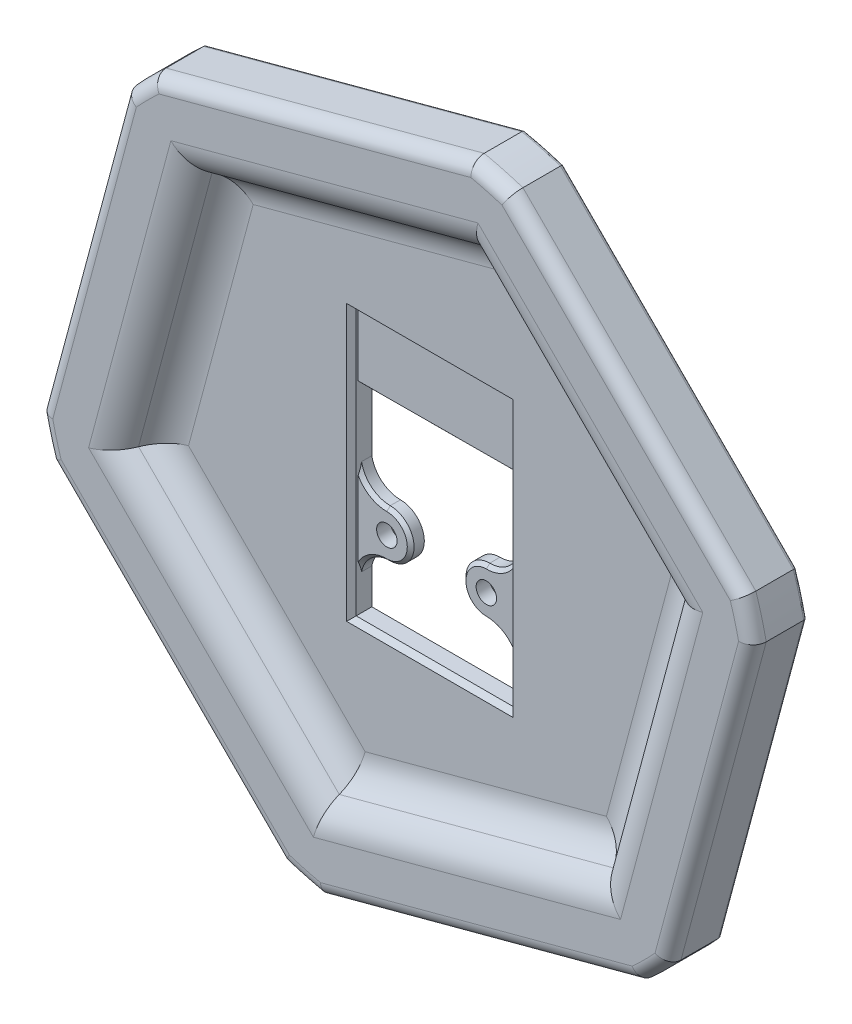
SolidWorks part; units mm, degrees
ref_plane "Спереди" through (0, 0, 0) normal (0, 0, 1) x (1, 0, 0)
ref_plane "Сверху" through (0, 0, 0) normal (0, 1, 0) x (1, 0, 0)
ref_plane "Справа" through (0, 0, 0) normal (1, 0, 0) x (0, 0, -1)
sketch "Эскиз1" plane through (0, 0, 0) normal (0, 0, 1) x (1, 0, 0)
  circle A1 centre (0, 0) radius 53.5
  circle A5 centre (0, 0) radius 39
extrude "Бобышка-Вытянуть1" add sketch "Эскиз1" along normal blind 65
sketch "Эскиз2" plane through (0, 0, 65) normal (0, 0, 1) x (1, 0, 0)
  line L0 (0, 0) -> (-8, 8) construction
  line L1 (-8, 8) -> (-59.1146, 59.1146) construction
  line L2 (-34.0759, 34.0759) -> (-46.5485, -12.4726)
  line L3 (-35.7089, 35.7089) -> (-48.7793, -13.0704)
  line L4 (-48.7793, -13.0704) -> (-13.0704, -48.7793)
  line L5 (-13.0704, -48.7793) -> (35.7089, -35.7089)
  line L6 (35.7089, -35.7089) -> (48.7793, 13.0704)
  line L7 (48.7793, 13.0704) -> (13.0704, 48.7793)
  line L8 (13.0704, 48.7793) -> (-35.7089, 35.7089)
  line L9 (-46.5485, -12.4726) -> (-12.4726, -46.5485)
  line L10 (-12.4726, -46.5485) -> (34.0759, -34.0759)
  line L11 (34.0759, -34.0759) -> (46.5485, 12.4726)
  line L12 (46.5485, 12.4726) -> (12.4726, 46.5485)
  line L13 (12.4726, 46.5485) -> (-34.0759, 34.0759)
  circle A0 centre (0, 0) radius 43.7343 construction
  dimension "D1" = 101
  dimension "D2" = 2
extrude "Вырез-Вытянуть1" cut sketch "Эскиз2" against normal blind 3
sketch "Эскиз3" plane through (0, 0, 65) normal (0, 0, 1) x (1, 0, 0)
  line L0 (43.7602, 11.7255) -> (11.7255, 43.7602)
  line L1 (11.7255, 43.7602) -> (-32.0347, 32.0347)
  line L2 (-32.0347, 32.0347) -> (-43.7602, -11.7255)
  line L3 (-43.7602, -11.7255) -> (-11.7255, -43.7602)
  line L4 (-11.7255, -43.7602) -> (32.0347, -32.0347)
  line L5 (32.0347, -32.0347) -> (43.7602, 11.7255)
  line L6 (46.5485, 12.4726) -> (12.4726, 46.5485)
  line L7 (12.4726, 46.5485) -> (-34.0759, 34.0759)
  line L8 (-34.0759, 34.0759) -> (-46.5485, -12.4726)
  line L9 (-46.5485, -12.4726) -> (-12.4726, -46.5485)
  line L10 (-12.4726, -46.5485) -> (34.0759, -34.0759)
  line L11 (34.0759, -34.0759) -> (46.5485, 12.4726)
  line L12 (46.5485, 12.4726) -> (12.4726, 46.5485)
  line L13 (12.4726, 46.5485) -> (-34.0759, 34.0759)
  line L14 (-34.0759, 34.0759) -> (-46.5485, -12.4726)
  line L15 (-46.5485, -12.4726) -> (-12.4726, -46.5485)
  line L16 (-12.4726, -46.5485) -> (34.0759, -34.0759)
  line L17 (34.0759, -34.0759) -> (46.5485, 12.4726)
  dimension "D1" = 0
  dimension "D2" = 2.5
extrude "Бобышка-Вытянуть2" add sketch "Эскиз3" along normal blind 3
fillet "Скругление2" radius 3 1 edges at (39, 0, 65)
sketch "Эскиз4" plane through (0, 0, 65) normal (0, 0, 1) x (1, 0, 0)
  line L12 (14.2658, 53.2407) -> (-38.9749, 38.9749)
  line L13 (53.2407, 14.2658) -> (14.2658, 53.2407)
  line L14 (38.9749, -38.9749) -> (53.2407, 14.2658)
  line L15 (-14.2658, -53.2407) -> (38.9749, -38.9749)
  line L16 (-53.2407, -14.2658) -> (-14.2658, -53.2407)
  line L17 (-38.9749, 38.9749) -> (-53.2407, -14.2658)
  line L18 (14.2658, 53.2407) -> (-38.9749, 38.9749)
  line L19 (53.2407, 14.2658) -> (14.2658, 53.2407)
  line L20 (38.9749, -38.9749) -> (53.2407, 14.2658)
  line L21 (-14.2658, -53.2407) -> (38.9749, -38.9749)
  line L22 (-53.2407, -14.2658) -> (-14.2658, -53.2407)
  line L23 (-38.9749, 38.9749) -> (-53.2407, -14.2658)
  circle A2 centre (0, 0) radius 58.5
  circle A3 centre (0, 0) radius 58.5
  dimension "D1" = 4
  dimension "D2" = 5
extrude "Вырез-Вытянуть2" cut sketch "Эскиз4" against normal blind 105 contours L18 L23 L22 L21 L20 L19 | A3
fillet "Скругление3" radius 2 12 edges at (13.8468, 51.677, 65) (-12.3545, 46.1078, 65) (-37.8302, 37.8302, 65) (-46.1078, 12.3545, 65) (-51.677, -13.8468, 65) (-33.7532, -33.7532, 65) (-13.8468, -51.677, 65) (37.8302, -37.8302, 65) (12.3545, -46.1078, 65) (33.7532, 33.7532, 65) (51.677, 13.8468, 65) (46.1078, -12.3545, 65)
sketch "Эскиз5" plane through (0, 0, 65) normal (0, 0, 1) x (1, 0, 0)
  line L2 (-11.7255, -43.7602) -> (-4.3237, -41.7769)
  line L3 (-17.144, -38.3417) -> (-11.7255, -43.7602)
  line L4 (-11.7255, -43.7602) -> (-4.3237, -41.7769)
  line L5 (-17.144, -38.3417) -> (-11.7255, -43.7602)
  line L8 (-43.7602, -11.7255) -> (-38.3417, -17.144)
  line L9 (-41.7769, -4.3237) -> (-43.7602, -11.7255)
  line L12 (-32.0347, 32.0347) -> (-34.018, 24.6329)
  line L13 (-24.6329, 34.018) -> (-32.0347, 32.0347)
  line L16 (11.7255, 43.7602) -> (4.3237, 41.7769)
  line L17 (17.144, 38.3417) -> (11.7255, 43.7602)
  line L20 (43.7602, 11.7255) -> (38.3417, 17.144)
  line L21 (41.7769, 4.3237) -> (43.7602, 11.7255)
  line L24 (32.0347, -32.0347) -> (34.018, -24.6329)
  line L25 (24.6329, -34.018) -> (32.0347, -32.0347)
  arc A1 (-17.144, -38.3417) -> (-4.3237, -41.7769) centre (0, 0) ccw
  arc A3 (-17.144, -38.3417) -> (-4.3237, -41.7769) centre (0, 0) ccw
  arc A4 (-41.7769, -4.3237) -> (-38.3417, -17.144) centre (0, 0) ccw
  arc A6 (-24.6329, 34.018) -> (-34.018, 24.6329) centre (0, 0) ccw
  arc A8 (17.144, 38.3417) -> (4.3237, 41.7769) centre (0, 0) ccw
  arc A10 (41.7769, 4.3237) -> (38.3417, 17.144) centre (0, 0) ccw
  arc A12 (24.6329, -34.018) -> (34.018, -24.6329) centre (0, 0) ccw
  dimension "D1" = 0
extrude "Бобышка-Вытянуть3" add sketch "Эскиз5" along normal blind 3
sketch "Эскиз6" plane through (0, 0, 0) normal (0, 0, -1) x (-1, 0, 0)
  circle A0 centre (-11.841, 44.1911) radius 1.25 construction
  circle A1 centre (32.3501, 32.3501) radius 1.25 construction
  circle A2 centre (44.1911, -11.841) radius 1.25 construction
  circle A3 centre (11.841, -44.1911) radius 1.25 construction
  circle A4 centre (-32.3501, -32.3501) radius 1.25 construction
  circle A5 centre (-44.1911, 11.841) radius 1.25 construction
  circle A6 centre (-11.841, 44.1911) radius 1.25
  circle A7 centre (32.3501, 32.3501) radius 1.25
  circle A8 centre (44.1911, -11.841) radius 1.25
  circle A9 centre (11.841, -44.1911) radius 1.25
  circle A10 centre (-32.3501, -32.3501) radius 1.25
  circle A11 centre (-44.1911, 11.841) radius 1.25
extrude "Вырез-Вытянуть3" cut sketch "Эскиз6" against normal blind 15
sketch "Эскиз7" plane through (-12.3545, 46.1078, 0) normal (-0.2588, 0.9659, 0) x (0.9659, 0.2588, 0)
  line L3 (0, 0) -> (0, -5) construction
  line L4 (0, -5) -> (0, -78.0432) construction
  circle A0 centre (0, -17) radius 8
  point P2 (0, -5)
  point P6 (0, -17)
  dimension "D2" = 16
  dimension "D1" = 12
extrude "Вырез-Вытянуть4" cut sketch "Эскиз7" against normal blind 10 contours A0
sketch "Эскиз9" plane through (-12.3545, 46.1078, 0) normal (-0.2588, 0.9659, 0) x (0.9659, 0.2588, 0)
  circle A2 centre (0, -17) radius 6
  dimension "D1" = 12
extrude "Вытянуть-Тонкостенный1" add sketch "Эскиз9" against normal blind 6 thin thin type one direction wall 3
sketch "Эскиз10" plane through (-12.3545, 46.1078, 0) normal (-0.2588, 0.9659, 0) x (0.9659, 0.2588, 0)
  circle A2 centre (0, -17) radius 8.5
  dimension "D1" = 17
extrude "Вырез-Вытянуть5" cut sketch "Эскиз10" against normal blind 2
sketch "Эскиз11" plane through (0, 0, 0) normal (0, 0, -1) x (-1, 0, 0)
  line L7 (-16.6698, 50.8367) -> (-50.8367, 16.6698)
  line L8 (-52.3608, 10.9819) -> (-39.8548, -35.691)
  line L9 (-35.691, -39.8548) -> (10.9819, -52.3608)
  line L10 (16.6698, -50.8367) -> (50.8367, -16.6698)
  line L11 (52.3608, -10.9819) -> (39.8548, 35.691)
  line L12 (35.691, 39.8548) -> (-10.9819, 52.3608)
  line L13 (-16.6698, 50.8367) -> (-50.8367, 16.6698)
  line L14 (-52.3608, 10.9819) -> (-39.8548, -35.691)
  line L15 (-35.691, -39.8548) -> (10.9819, -52.3608)
  line L16 (16.6698, -50.8367) -> (50.8367, -16.6698)
  line L17 (52.3608, -10.9819) -> (39.8548, 35.691)
  line L18 (35.691, 39.8548) -> (-10.9819, 52.3608)
  arc A7 (-50.8367, 16.6698) -> (-52.3608, 10.9819) centre (0, 0) ccw
  arc A8 (-39.8548, -35.691) -> (-35.691, -39.8548) centre (0, 0) ccw
  arc A9 (10.9819, -52.3608) -> (16.6698, -50.8367) centre (0, 0) ccw
  arc A10 (50.8367, -16.6698) -> (52.3608, -10.9819) centre (0, 0) ccw
  arc A11 (39.8548, 35.691) -> (35.691, 39.8548) centre (0, 0) ccw
  arc A12 (-10.9819, 52.3608) -> (-16.6698, 50.8367) centre (0, 0) ccw
  arc A13 (-50.8367, 16.6698) -> (-52.3608, 10.9819) centre (0, 0) ccw
  arc A14 (-39.8548, -35.691) -> (-35.691, -39.8548) centre (0, 0) ccw
  arc A15 (10.9819, -52.3608) -> (16.6698, -50.8367) centre (0, 0) ccw
  arc A16 (50.8367, -16.6698) -> (52.3608, -10.9819) centre (0, 0) ccw
  arc A17 (39.8548, 35.691) -> (35.691, 39.8548) centre (0, 0) ccw
  arc A18 (-10.9819, 52.3608) -> (-16.6698, 50.8367) centre (0, 0) ccw
  dimension "D1" = 0
extrude "Вырез-Вытянуть6" cut sketch "Эскиз11" against normal blind 50
sketch "Эскиз13" plane through (0, 0, 50) normal (0, 0, -1) x (-1, 0, 0)
  line L0 (35.7089, 35.7089) -> (48.7793, -13.0704) construction
  line L1 (48.7793, -13.0704) -> (13.0704, -48.7793) construction
  line L2 (13.0704, -48.7793) -> (-35.7089, -35.7089) construction
  line L3 (-35.7089, -35.7089) -> (-48.7793, 13.0704) construction
  line L4 (-13.0704, 48.7793) -> (35.7089, 35.7089) construction
  line L5 (-48.7793, 13.0704) -> (-13.0704, 48.7793) construction
  line L6 (35.7089, 35.7089) -> (48.7793, -13.0704)
  line L7 (48.7793, -13.0704) -> (13.0704, -48.7793)
  line L8 (13.0704, -48.7793) -> (-35.7089, -35.7089)
  line L9 (-35.7089, -35.7089) -> (-48.7793, 13.0704)
  line L10 (-13.0704, 48.7793) -> (35.7089, 35.7089)
  line L11 (-48.7793, 13.0704) -> (-13.0704, 48.7793)
  line L24 (45.4332, -12.1738) -> (33.2594, 33.2594)
  line L25 (12.1738, -45.4332) -> (45.4332, -12.1738)
  line L26 (-33.2594, -33.2594) -> (12.1738, -45.4332)
  line L27 (-45.4332, 12.1738) -> (-33.2594, -33.2594)
  line L28 (-12.1738, 45.4332) -> (-45.4332, 12.1738)
  line L29 (33.2594, 33.2594) -> (-12.1738, 45.4332)
  line L30 (45.4332, -12.1738) -> (33.2594, 33.2594)
  line L31 (12.1738, -45.4332) -> (45.4332, -12.1738)
  line L32 (-33.2594, -33.2594) -> (12.1738, -45.4332)
  line L33 (-45.4332, 12.1738) -> (-33.2594, -33.2594)
  line L34 (-12.1738, 45.4332) -> (-45.4332, 12.1738)
  line L35 (33.2594, 33.2594) -> (-12.1738, 45.4332)
  dimension "D1" = 1
extrude "Вырез-Вытянуть7" cut sketch "Эскиз13" against normal blind 6
fillet "Скругление4" radius 1 1 edges at (-39, 0, 50)
fillet "Скругление5" radius 0.5 6 edges at (-42.2441, 11.3193, 56) (-30.9248, -30.9248, 50) (11.3193, -42.2441, 50) (42.2441, -11.3193, 50) (30.9248, 30.9248, 50) (-11.3193, 42.2441, 50)
fillet "Скругление6" radius 0.5 6 edges at (39.3463, -10.5428, 50) (10.5428, -39.3463, 56) (-28.8035, -28.8035, 50) (-39.3463, 10.5428, 56) (-10.5428, 39.3463, 56) (28.8035, 28.8035, 50)
sketch "Эскиз14" plane through (0, 0, 65) normal (0, 0, 1) x (1, 0, 0)
  line L0 (-38.0477, 34.7076) -> (-50.3041, -11.0338) construction
  line L1 (11.0338, 50.3041) -> (-34.7076, 38.0477) construction
  line L2 (49.0816, 15.5965) -> (15.5965, 49.0816) construction
  line L3 (38.0477, -34.7076) -> (50.3041, 11.0338) construction
  line L4 (-49.0816, -15.5965) -> (-15.5965, -49.0816) construction
  line L5 (-11.0338, -50.3041) -> (34.7076, -38.0477) construction
  line L6 (-38.0477, 34.7076) -> (-50.3041, -11.0338)
  line L7 (11.0338, 50.3041) -> (-34.7076, 38.0477)
  line L8 (49.0816, 15.5965) -> (15.5965, 49.0816)
  line L9 (38.0477, -34.7076) -> (50.3041, 11.0338)
  line L10 (-49.0816, -15.5965) -> (-15.5965, -49.0816)
  line L11 (-11.0338, -50.3041) -> (34.7076, -38.0477)
  arc A0 (-50.3041, -11.0338) -> (-49.0816, -15.5965) centre (0, 0) ccw construction
  arc A1 (-34.7076, 38.0477) -> (-38.0477, 34.7076) centre (0, 0) ccw construction
  arc A2 (15.5965, 49.0816) -> (11.0338, 50.3041) centre (0, 0) ccw construction
  arc A3 (50.3041, 11.0338) -> (49.0816, 15.5965) centre (0, 0) ccw construction
  arc A4 (34.7076, -38.0477) -> (38.0477, -34.7076) centre (0, 0) ccw construction
  arc A5 (-15.5965, -49.0816) -> (-11.0338, -50.3041) centre (0, 0) ccw construction
  arc A6 (-50.3041, -11.0338) -> (-49.0816, -15.5965) centre (0, 0) ccw
  arc A7 (-34.7076, 38.0477) -> (-38.0477, 34.7076) centre (0, 0) ccw
  arc A8 (15.5965, 49.0816) -> (11.0338, 50.3041) centre (0, 0) ccw
  arc A9 (50.3041, 11.0338) -> (49.0816, 15.5965) centre (0, 0) ccw
  arc A10 (34.7076, -38.0477) -> (38.0477, -34.7076) centre (0, 0) ccw
  arc A11 (-15.5965, -49.0816) -> (-11.0338, -50.3041) centre (0, 0) ccw
extrude "Вырез-Вытянуть8" cut sketch "Эскиз14" along normal blind 5
sketch "Эскиз16" plane through (0, 0, 50) normal (0, 0, -1) x (-1, 0, 0)
  line L6 (-16.6698, 50.8367) -> (-50.8367, 16.6698)
  line L7 (-52.3608, 10.9819) -> (-39.8548, -35.691)
  line L8 (-35.691, -39.8548) -> (10.9819, -52.3608)
  line L9 (16.6698, -50.8367) -> (50.8367, -16.6698)
  line L10 (52.3608, -10.9819) -> (39.8548, 35.691)
  line L11 (35.691, 39.8548) -> (-10.9819, 52.3608)
  line L12 (-16.6698, 50.8367) -> (-50.8367, 16.6698)
  line L13 (-52.3608, 10.9819) -> (-39.8548, -35.691)
  line L14 (-35.691, -39.8548) -> (10.9819, -52.3608)
  line L15 (16.6698, -50.8367) -> (50.8367, -16.6698)
  line L16 (52.3608, -10.9819) -> (39.8548, 35.691)
  line L17 (35.691, 39.8548) -> (-10.9819, 52.3608)
  arc A6 (-10.9819, 52.3608) -> (-16.6698, 50.8367) centre (0, 0) ccw
  arc A7 (-50.8367, 16.6698) -> (-52.3608, 10.9819) centre (0, 0) ccw
  arc A8 (-39.8548, -35.691) -> (-35.691, -39.8548) centre (0, 0) ccw
  arc A9 (10.9819, -52.3608) -> (16.6698, -50.8367) centre (0, 0) ccw
  arc A10 (50.8367, -16.6698) -> (52.3608, -10.9819) centre (0, 0) ccw
  arc A11 (39.8548, 35.691) -> (35.691, 39.8548) centre (0, 0) ccw
  arc A12 (-10.9819, 52.3608) -> (-16.6698, 50.8367) centre (0, 0) ccw
  arc A13 (-50.8367, 16.6698) -> (-52.3608, 10.9819) centre (0, 0) ccw
  arc A14 (-39.8548, -35.691) -> (-35.691, -39.8548) centre (0, 0) ccw
  arc A15 (10.9819, -52.3608) -> (16.6698, -50.8367) centre (0, 0) ccw
  arc A16 (50.8367, -16.6698) -> (52.3608, -10.9819) centre (0, 0) ccw
  arc A17 (39.8548, 35.691) -> (35.691, 39.8548) centre (0, 0) ccw
  dimension "D1" = 0
extrude "Вырез-Вытянуть9" cut sketch "Эскиз16" against normal blind 5
sketch "Эскиз23" plane through (0, 0, 56) normal (0, 0, -1) x (-1, 0, 0)
  line L0 (13.0704, -48.7793) -> (48.371, -13.4786) construction
  line L1 (45.4332, -12.1738) -> (12.1738, -45.4332) construction
  line L2 (12.1738, -45.4332) -> (-33.2594, -33.2594) construction
  line L3 (-33.2594, -33.2594) -> (-45.4332, 12.1738) construction
  line L4 (-35.7089, -35.7089) -> (-48.7793, 13.0704) construction
  line L5 (-35.7089, -35.7089) -> (13.0704, -48.7793) construction
  line L6 (13.0704, -48.7793) -> (48.371, -13.4786)
  line L7 (45.4332, -12.1738) -> (12.1738, -45.4332)
  line L8 (12.1738, -45.4332) -> (-33.2594, -33.2594)
  line L9 (-33.2594, -33.2594) -> (-45.4332, 12.1738)
  line L10 (-35.7089, -35.7089) -> (-48.7793, 13.0704)
  line L11 (-35.7089, -35.7089) -> (13.0704, -48.7793)
  line L12 (-45.4332, 12.1738) -> (-12.1738, 45.4332) construction
  line L13 (-48.7793, 13.0704) -> (-13.0704, 48.7793) construction
  line L14 (-45.4332, 12.1738) -> (-12.1738, 45.4332)
  line L15 (-48.7793, 13.0704) -> (-13.0704, 48.7793)
  line L16 (33.2594, 33.2594) -> (-12.1738, 45.4332) construction
  line L17 (-13.0704, 48.7793) -> (35.7089, 35.7089) construction
  line L18 (33.2594, 33.2594) -> (-12.1738, 45.4332)
  line L19 (-13.0704, 48.7793) -> (35.7089, 35.7089)
  line L20 (33.2594, 33.2594) -> (45.4332, -12.1738) construction
  line L21 (35.7089, 35.7089) -> (48.7793, -13.0704) construction
  line L22 (33.2594, 33.2594) -> (45.4332, -12.1738)
  line L23 (35.7089, 35.7089) -> (48.7793, -13.0704)
  line M7 (45.8414, -11.7655) -> (11.7655, -45.8414)
  line M8 (11.7655, -45.8414) -> (-33.11, -33.8171)
  line M9 (-33.11, -33.8171) -> (-45.4332, 12.1738)
  line M10 (-45.4332, 12.1738) -> (-11.7655, 45.8414)
  line M11 (-11.7655, 45.8414) -> (33.6677, 33.6677)
  line M12 (33.6677, 33.6677) -> (45.8414, -11.7655)
  line M13 (13.0704, -48.7793) -> (48.371, -13.4786)
  line M14 (48.371, -13.4786) -> (35.1512, 35.8583)
  line M15 (35.1512, 35.8583) -> (-13.0704, 48.7793)
  line M16 (-13.0704, 48.7793) -> (-48.7793, 13.0704)
  line M17 (-48.7793, 13.0704) -> (-35.7089, -35.7089)
  line M18 (-35.7089, -35.7089) -> (13.0704, -48.7793)
extrude "Вырез-Вытянуть11" cut sketch "Эскиз23" against normal blind 4 contours M18 M13 M14 M15 M16 M17 M12 M7 M8 M9 M10 M11 region at (10.9629, -40.9142, 56)
sketch "Эскиз25" plane through (0, 0, 55) normal (0, 0, -1) x (-1, 0, 0)
  line L0 (-35.691, -39.8548) -> (10.9819, -52.3608) construction
  line L1 (16.6698, -50.8367) -> (50.8367, -16.6698) construction
  line L2 (52.3608, -10.9819) -> (39.8548, 35.691) construction
  line L3 (35.691, 39.8548) -> (-10.9819, 52.3608) construction
  line L4 (-16.6698, 50.8367) -> (-50.8367, 16.6698) construction
  line L5 (-52.3608, 10.9819) -> (-39.8548, -35.691) construction
  line L6 (-35.691, -39.8548) -> (10.9819, -52.3608)
  line L7 (16.6698, -50.8367) -> (50.8367, -16.6698)
  line L8 (52.3608, -10.9819) -> (39.8548, 35.691)
  line L9 (35.691, 39.8548) -> (-10.9819, 52.3608)
  line L10 (-16.6698, 50.8367) -> (-50.8367, 16.6698)
  line L11 (-52.3608, 10.9819) -> (-39.8548, -35.691)
  arc A0 (-39.8548, -35.691) -> (-35.691, -39.8548) centre (0, 0) ccw construction
  arc A1 (10.9819, -52.3608) -> (16.6698, -50.8367) centre (0, 0) ccw construction
  arc A2 (50.8367, -16.6698) -> (52.3608, -10.9819) centre (0, 0) ccw construction
  arc A3 (39.8548, 35.691) -> (35.691, 39.8548) centre (0, 0) ccw construction
  arc A4 (-10.9819, 52.3608) -> (-16.6698, 50.8367) centre (0, 0) ccw construction
  arc A5 (-50.8367, 16.6698) -> (-52.3608, 10.9819) centre (0, 0) ccw construction
  arc A6 (-39.8548, -35.691) -> (-35.691, -39.8548) centre (0, 0) ccw
  arc A7 (10.9819, -52.3608) -> (16.6698, -50.8367) centre (0, 0) ccw
  arc A8 (50.8367, -16.6698) -> (52.3608, -10.9819) centre (0, 0) ccw
  arc A9 (39.8548, 35.691) -> (35.691, 39.8548) centre (0, 0) ccw
  arc A10 (-10.9819, 52.3608) -> (-16.6698, 50.8367) centre (0, 0) ccw
  arc A11 (-50.8367, 16.6698) -> (-52.3608, 10.9819) centre (0, 0) ccw
extrude "Вырез-Вытянуть12" cut sketch "Эскиз25" against normal blind 2
fillet "Скругление7" radius 0.5 19 edges at (-39, 0, 57) (42.2441, -11.3193, 57) (11.3193, -42.2441, 57) (-30.7207, -31.1289, 57) (-41.7611, 11.1899, 57) (-11.0404, 42.3188, 57) (30.9248, 30.9248, 57) (46.1078, -12.3545, 57) (51.677, 13.8468, 57) (33.7532, 33.7532, 57) (13.8468, 51.677, 57) (-12.3545, 46.1078, 57) (-37.8302, 37.8302, 57) (-46.1078, 12.3545, 57) (-51.677, -13.8468, 57) (-33.7532, -33.7532, 57) (-13.8468, -51.677, 57) (12.3545, -46.1078, 57) (37.8302, -37.8302, 57)
sketch "Эскиз27" plane through (0, 0, 57) normal (0, 0, -1) x (-1, 0, 0)
  line L12 (-31.477, -32.1841) -> (11.1678, -43.6107)
  line L13 (11.1678, -43.6107) -> (43.6107, -11.1678)
  line L14 (43.6107, -11.1678) -> (32.0347, 32.0347)
  line L15 (32.0347, 32.0347) -> (-11.1678, 43.6107)
  line L16 (-11.1678, 43.6107) -> (-43.2025, 11.5761)
  line L17 (-43.2025, 11.5761) -> (-31.477, -32.1841)
  line L18 (-31.477, -32.1841) -> (11.1678, -43.6107)
  line L19 (11.1678, -43.6107) -> (43.6107, -11.1678)
  line L20 (43.6107, -11.1678) -> (32.0347, 32.0347)
  line L21 (32.0347, 32.0347) -> (-11.1678, 43.6107)
  line L22 (-11.1678, 43.6107) -> (-43.2025, 11.5761)
  line L23 (-43.2025, 11.5761) -> (-31.477, -32.1841)
  dimension "D1" = 2
extrude "Вырез-Вытянуть13" cut sketch "Эскиз27" against normal blind 9
sketch "Эскиз28" plane through (0, 0, 65) normal (0, 0, 1) x (1, 0, 0)
  line L12 (-32.4429, 32.4429) -> (-44.3178, -11.8749)
  line L13 (11.8749, 44.3178) -> (-32.4429, 32.4429)
  line L14 (44.3178, 11.8749) -> (11.8749, 44.3178)
  line L15 (32.4429, -32.4429) -> (44.3178, 11.8749)
  line L16 (-11.8749, -44.3178) -> (32.4429, -32.4429)
  line L17 (-44.3178, -11.8749) -> (-11.8749, -44.3178)
  line L18 (-32.4429, 32.4429) -> (-44.3178, -11.8749)
  line L19 (11.8749, 44.3178) -> (-32.4429, 32.4429)
  line L20 (44.3178, 11.8749) -> (11.8749, 44.3178)
  line L21 (32.4429, -32.4429) -> (44.3178, 11.8749)
  line L22 (-11.8749, -44.3178) -> (32.4429, -32.4429)
  line L23 (-44.3178, -11.8749) -> (-11.8749, -44.3178)
  dimension "D1" = 2
extrude "Бобышка-Вытянуть4" add sketch "Эскиз28" against normal blind 8
sketch "Эскиз29" plane through (0, 0, 65) normal (0, 0, 1) x (1, 0, 0)
  line L12 (-29.9934, 29.9934) -> (-40.9718, -10.9784)
  line L13 (-40.9718, -10.9784) -> (-10.9784, -40.9718)
  line L14 (-10.9784, -40.9718) -> (29.9934, -29.9934)
  line L15 (29.9934, -29.9934) -> (40.9718, 10.9784)
  line L16 (40.9718, 10.9784) -> (10.9784, 40.9718)
  line L17 (10.9784, 40.9718) -> (-29.9934, 29.9934)
  line L18 (-29.9934, 29.9934) -> (-40.9718, -10.9784)
  line L19 (-40.9718, -10.9784) -> (-10.9784, -40.9718)
  line L20 (-10.9784, -40.9718) -> (29.9934, -29.9934)
  line L21 (29.9934, -29.9934) -> (40.9718, 10.9784)
  line L22 (40.9718, 10.9784) -> (10.9784, 40.9718)
  line L23 (10.9784, 40.9718) -> (-29.9934, 29.9934)
  dimension "D1" = 5
extrude "Вырез-Вытянуть14" cut sketch "Эскиз29" against normal blind 5
sketch "Эскиз31" plane through (0, 0, 62) normal (0, 0, 1) x (1, 0, 0)
  line L0 (-13.0704, -48.7793) -> (35.7089, -35.7089) construction
  line L1 (-12.4726, -46.5485) -> (34.0759, -34.0759) construction
  line L2 (-12.4726, -46.5485) -> (-46.5485, -12.4726) construction
  line L3 (-48.7793, -13.0704) -> (-13.0704, -48.7793) construction
  line L4 (-46.5485, -12.4726) -> (-34.0759, 34.0759) construction
  line L5 (-35.7089, 35.7089) -> (-48.7793, -13.0704) construction
  line L6 (-34.0759, 34.0759) -> (12.4726, 46.5485) construction
  line L7 (13.0704, 48.7793) -> (-35.7089, 35.7089) construction
  line L8 (12.4726, 46.5485) -> (46.5485, 12.4726) construction
  line L9 (48.7793, 13.0704) -> (13.0704, 48.7793) construction
  line L10 (46.5485, 12.4726) -> (34.0759, -34.0759) construction
  line L11 (35.7089, -35.7089) -> (48.7793, 13.0704) construction
  line L12 (-13.0704, -48.7793) -> (35.7089, -35.7089)
  line L13 (-12.4726, -46.5485) -> (34.0759, -34.0759)
  line L14 (-12.4726, -46.5485) -> (-46.5485, -12.4726)
  line L15 (-48.7793, -13.0704) -> (-13.0704, -48.7793)
  line L16 (-46.5485, -12.4726) -> (-34.0759, 34.0759)
  line L17 (-35.7089, 35.7089) -> (-48.7793, -13.0704)
  line L18 (-34.0759, 34.0759) -> (12.4726, 46.5485)
  line L19 (13.0704, 48.7793) -> (-35.7089, 35.7089)
  line L20 (12.4726, 46.5485) -> (46.5485, 12.4726)
  line L21 (48.7793, 13.0704) -> (13.0704, 48.7793)
  line L22 (46.5485, 12.4726) -> (34.0759, -34.0759)
  line L23 (35.7089, -35.7089) -> (48.7793, 13.0704)
extrude "Бобышка-Вытянуть5" add sketch "Эскиз31" along normal blind 3
fillet "Скругление8" radius 5 6 edges at (25.9751, 25.9751, 60) (35.4826, -9.5075, 60) (9.5075, -35.4826, 60) (-25.9751, -25.9751, 60) (-35.4826, 9.5075, 60) (-9.5075, 35.4826, 60)
fillet "Скругление9" radius 5 6 edges at (-9.5075, 35.4826, 65) (25.9751, 25.9751, 65) (35.4826, -9.5075, 65) (9.5075, -35.4826, 65) (-25.9751, -25.9751, 65) (-35.4826, 9.5075, 65)
sketch "Эскиз32" plane through (0, 0, 60) normal (0, 0, 1) x (1, 0, 0)
  line L0 (0, 0) -> (0, -58.7339) construction
  line L1 (0, 0) -> (0, 54.5809) construction
  line L2 (0, 0) -> (76.2602, 0) construction
  line L3 (0, 0) -> (-67.0063, 0) construction
  line L5 (-11.5, 19.5) -> (11.5, 19.5)
  line L6 (-11.5, 19.5) -> (-11.5, -19.5)
  line L7 (-11.5, -19.5) -> (11.5, -19.5)
  line L8 (11.5, 19.5) -> (11.5, -19.5)
  line L9 (-11.5, 19.5) -> (11.5, -19.5) construction
  line L10 (-11.5, -19.5) -> (11.5, 19.5) construction
  dimension "D1" = 23
  dimension "D2" = 39
extrude "Вырез-Вытянуть15" cut sketch "Эскиз32" against normal blind 8
sketch "Эскиз33" plane through (0, 0, 60) normal (0, 0, 1) x (1, 0, 0)
  line L0 (11.5, 19.5) -> (-11.5, 19.5) construction
  line L1 (-11.5, 19.5) -> (-11.5, -19.5) construction
  line L2 (-11.5, -19.5) -> (11.5, -19.5) construction
  line L3 (11.5, -19.5) -> (11.5, 19.5) construction
  line L4 (11.5, 19.5) -> (-11.5, 19.5) construction
  line L5 (-11.5, 19.5) -> (-11.5, -19.5) construction
  line L6 (-11.5, -19.5) -> (11.5, -19.5) construction
  line L7 (11.5, -19.5) -> (11.5, 19.5) construction
  circle A0 centre (-7.3, -7.3) radius 1.5
  circle A1 centre (7.3, -7.3) radius 1.5
  point P2 (7.3, -7.3)
  point P5 (-7.3, -7.3)
  dimension "D5" = 3
  dimension "D1" = 26.8
  dimension "D2" = 4.2
  dimension "D3" = 26.8
  dimension "D4" = 4.2
extrude "Вытянуть-Тонкостенный2" add sketch "Эскиз33" against normal blind 3 separate body thin thin type one direction wall 2
sketch "Эскиз34" plane through (0, 0, 60) normal (0, 0, 1) x (1, 0, 0)
  line L2 (11.5, -19.5) -> (11.5, 19.5) construction
  line L3 (11.5, -14.3) -> (11.5, -0.3)
  line L4 (-7.3, -7.3) -> (-7.3, -1.0126) construction
  line L5 (-7.3, -7.3) -> (-7.3, -12.8615) construction
  line L6 (7.3, -7.3) -> (7.3, -13.9535) construction
  line L7 (7.3, -7.3) -> (7.3, -0.4119) construction
  line L8 (-7.3, -7.3) -> (7.3, -7.3) construction
  line L9 (7.3, -7.3) -> (14.773, -7.3) construction
  line L10 (-7.3, -7.3) -> (-13.5056, -7.3) construction
  line L11 (-11.5, 19.5) -> (-11.5, -19.5) construction
  line L12 (-11.5, -0.3) -> (-11.5, -14.3)
  arc A4 (-7.3, -3.8) -> (-11.5, -0.3) centre (-7.3, 0.47) cw
  arc A5 (-7.3, -10.8) -> (-11.5, -14.3) centre (-7.3, -15.07) ccw
  arc A6 (7.3, -3.8) -> (11.5, -0.3) centre (7.3, 0.47) ccw
  arc A7 (7.3, -10.8) -> (11.5, -14.3) centre (7.3, -15.07) cw
  circle A8 centre (-7.3, -7.3) radius 3.5 construction
  circle A9 centre (7.3, -7.3) radius 3.5 construction
  arc A10 (-7.3, -3.8) -> (-7.3, -10.8) centre (-7.3, -7.3) ccw
  arc A11 (7.3, -10.8) -> (7.3, -3.8) centre (7.3, -7.3) ccw
  point P10 (7.3, -3.8)
  point P15 (7.3, -10.8)
  point P16 (-7.3, -10.8)
  point P17 (-7.3, -3.8)
  point P18 (11.5, -0.3)
  point P21 (11.5, -14.3)
  point P22 (-11.5, -0.3)
  point P23 (-11.5, -14.3)
  point P24 (-11.5, -7.3)
  point P25 (11.5, -7.3)
  dimension "D1" = 7
  dimension "D2" = 7
  dimension "D3" = 7
  dimension "D4" = 7
extrude "Бобышка-Вытянуть6" add sketch "Эскиз34" against normal blind 3
sketch "Эскиз35" plane through (0, 0, 60) normal (0, 0, 1) x (1, 0, 0)
  line L0 (-11.5, -14.3) -> (-11.5, -19.5) construction
  line L1 (-11.5, -19.5) -> (11.5, -19.5) construction
  line L2 (11.5, -19.5) -> (11.5, -14.3) construction
  line L3 (11.5, -0.3) -> (11.5, 19.5) construction
  line L4 (-11.5, 19.5) -> (-11.5, -0.3) construction
  line L5 (11.5, 19.5) -> (-11.5, 19.5) construction
  line L6 (-11.5, -14.3) -> (-11.5, -19.5)
  line L7 (-11.5, -19.5) -> (11.5, -19.5)
  line L8 (11.5, -19.5) -> (11.5, -14.3)
  line L9 (11.5, -0.3) -> (11.5, 19.5)
  line L10 (-11.5, 19.5) -> (-11.5, -0.3)
  line L11 (11.5, 19.5) -> (-11.5, 19.5)
  line L12 (-11.5, -0.3) -> (-11.5, -14.3)
  line L13 (11.5, -0.3) -> (11.5, -14.3)
extrude "Вырез-Вытянуть16" cut sketch "Эскиз35" against normal blind 1
chamfer "Фаска1" distance 0.7 4 edges at (11.5, 0, 60) (0, 19.5, 60) (-11.5, 0, 60) (0, -19.5, 60)
chamfer "Фаска2" distance 0.5 angle 45 3 edges at (-10.0336, -2.8103, 59) (-10.0336, -11.7897, 59) (-3.8, -7.3, 59)
chamfer "Фаска3" distance 0.5 angle 45 3 edges at (10.0336, -2.8103, 59) (10.0336, -11.7897, 59) (3.8, -7.3, 59)
sketch "Эскиз36" plane through (0, 0, 57) normal (0, 0, -1) x (-1, 0, 0)
  line L0 (11.5, 19.5) -> (-11.5, 19.5) construction
  line L1 (11.5, 19.5) -> (-11.5, 19.5)
  line L2 (-11.5, 19.5) -> (-11.5, -0.3) construction
  line L3 (-11.5, 19.5) -> (-11.5, 9.6)
  line L4 (11.5, -0.3) -> (11.5, 19.5) construction
  line L5 (11.5, 9.5) -> (11.5, 19.5)
  line L6 (-11.5, 9.6) -> (11.5, 9.5)
  point P4 (-11.5, 9.5)
  point P5 (11.5, 9.5)
  dimension "D1" = 10
  dimension "D2" = 10
extrude "Бобышка-Вытянуть7" add sketch "Эскиз36" against normal blind 2
chamfer "Фаска4" distance 0.7 angle 45 1 edges at (0, 9.55, 59)
